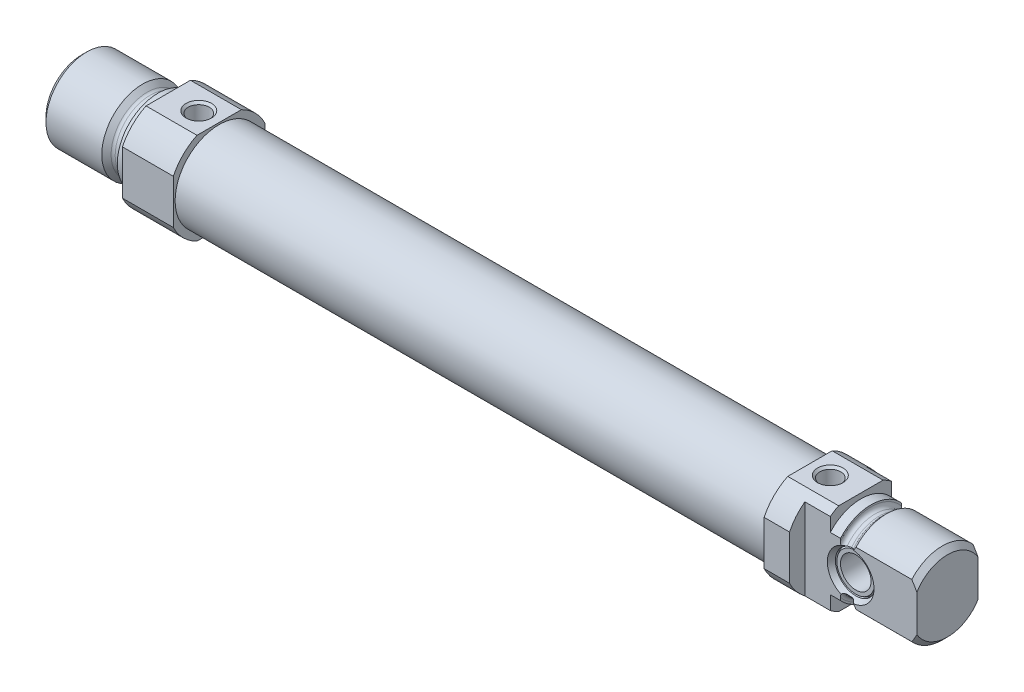
SolidWorks part; units mm, degrees
ref_plane "Front Plane" through (0, 0, 0) normal (0, 0, 1) x (1, 0, 0)
ref_plane "Top Plane" through (0, 0, 0) normal (0, 1, 0) x (1, 0, 0)
ref_plane "Right Plane" through (0, 0, 0) normal (1, 0, 0) x (0, 0, -1)
sketch "Sketch1" plane through (0, 0, 0) normal (0, 0, 1) x (1, 0, 0)
  line L0 (0, 0) -> (0, 7)
  line L1 (0, 7) -> (1, 8)
  line L2 (1, 8) -> (11.95, 8)
  line L3 (11.95, 8) -> (12.8657, 7.0843)
  line L4 (13.4314, 6.85) -> (14.2, 6.85)
  line L5 (15, 7.65) -> (15, 8)
  line L6 (15, 8) -> (17, 8)
  line L7 (17, 8) -> (17, 0)
  line L8 (17, 0) -> (0, 0)
  line L9 (17, 0) -> (0, 0) construction
  arc A0 (12.8657, 7.0843) -> (13.4314, 6.85) centre (13.4314, 7.65) ccw
  arc A1 (14.2, 6.85) -> (15, 7.65) centre (14.2, 7.65) ccw
revolve "Revolve1" add sketch "Sketch1" angle 360 about L9 reverse direction yes
cosmetic thread "Cosmetic Thread1" parameters "D1"=11.87, "D2"=14.16
ref_plane "Plane1" through (21.1, 0, 0) normal (1, 0, 0) x (0, 0, -1)
ref_plane "Plane2" through (9, 0, 0) normal (1, 0, 0) x (0, 0, -1)
ref_plane "Plane3" through (0, -11, 0) normal (0, 1, 0) x (1, 0, 0)
ref_plane "Plane4" through (0, 11, 0) normal (0, 1, 0) x (1, 0, 0)
ref_plane "Plane5" through (0, 0, 0) normal (0, 1, 0) x (1, 0, 0)
ref_plane "Plane6" through (0, 0, 0) normal (0, 1, 0) x (1, 0, 0)
ref_plane "Plane7" through (17, 0, 0) normal (1, 0, 0) x (0, 0, -1)
ref_plane "Plane8" through (17, 0, 0) normal (1, 0, 0) x (0, 0, -1)
ref_plane "Plane9" through (27, 0, 0) normal (1, 0, 0) x (0, 0, -1)
ref_plane "Plane10" through (17, 0, 0) normal (1, 0, 0) x (0, 0, -1)
ref_plane "Plane11" through (17, 0, 0) normal (1, 0, 0) x (0, 0, -1)
sketch "Sketch2" plane through (17, 0, 0) normal (1, 0, 0) x (0, 0, -1)
  line L0 (-4.3589, -9) -> (4.3589, -9)
  line L1 (9, -4.3589) -> (9, 4.3589)
  line L2 (4.3589, 9) -> (-4.3589, 9)
  line L3 (-9, 4.3589) -> (-9, -4.3589)
  arc A0 (-9, -4.3589) -> (-4.3589, -9) centre (0, 0) ccw
  arc A1 (4.3589, -9) -> (9, -4.3589) centre (0, 0) ccw
  arc A2 (9, 4.3589) -> (4.3589, 9) centre (0, 0) ccw
  arc A3 (-4.3589, 9) -> (-9, 4.3589) centre (0, 0) ccw
extrude "Boss-Extrude1" add sketch "Sketch2" along normal blind 10
ref_plane "Plane12" through (23, 0, 0) normal (1, 0, 0) x (0, 0, -1)
ref_plane "Plane13" through (0, 0, 0) normal (0, 0, 1) x (1, 0, 0)
ref_plane "Plane14" through (0, 0, -5.8) normal (0, 0, 1) x (1, 0, 0)
ref_plane "Plane15" through (0, 0, 0) normal (0, 1, 0) x (1, 0, 0)
ref_plane "Plane16" through (0, 4.5, 0) normal (0, 1, 0) x (1, 0, 0)
ref_plane "Plane17" through (0, 0, -6.6) normal (0, 0, 1) x (1, 0, 0)
ref_plane "Plane18" through (0, 0, 0) normal (0, 1, 0) x (1, 0, 0)
ref_plane "Plane19" through (0, 4.5, 0) normal (0, 1, 0) x (1, 0, 0)
ref_plane "Plane20" through (0, 5.493, -0.9686) normal (0, 0.9848, -0.1736) x (1, 0, 0)
ref_plane "Plane21" through (0, 4.0158, -0.7081) normal (0, 0.9848, -0.1736) x (1, 0, 0)
sketch "Sketch3" plane through (0, 0, 0) normal (0, 0, 1) x (1, 0, 0)
  line L0 (27, 0) -> (27, 8.65)
  line L1 (27, 8.65) -> (143, 8.65)
  line L2 (143, 8.65) -> (143, 0)
  line L3 (143, 0) -> (27, 0)
  line L4 (143, 0) -> (27, 0) construction
revolve "Revolve2" add sketch "Sketch3" angle 360 about L4 reverse direction yes
ref_plane "Plane22" through (143, 0, 0) normal (1, 0, 0) x (0, 0, -1)
sketch "Sketch4" plane through (143, 0, 0) normal (1, 0, 0) x (0, 0, -1)
  line L0 (-9, -9) -> (9, -9)
  line L1 (9, -9) -> (9, 9)
  line L2 (9, 9) -> (-9, 9)
  line L3 (-9, 9) -> (-9, -9)
extrude "Boss-Extrude2" add sketch "Sketch4" along normal blind 10
sketch "Sketch5" plane through (0, 0, 0) normal (0, 0, 1) x (1, 0, 0)
  line L0 (143, 20) -> (143, 10)
  line L1 (143, 10) -> (153, 10)
  line L2 (153, 10) -> (153, 20)
  line L3 (153, 20) -> (143, 20)
  line L4 (153, 0) -> (143, 0) construction
revolve "Cut-Revolve1" cut sketch "Sketch5" angle 360 about L4 reverse direction yes
ref_plane "Plane23" through (145.3, 0, 0) normal (1, 0, 0) x (0, 0, -1)
ref_plane "Plane24" through (147, 0, 0) normal (1, 0, 0) x (0, 0, -1)
ref_plane "Plane25" through (0, 0, 6.6) normal (0, 0, 1) x (1, 0, 0)
ref_plane "Plane26" through (0, 0, 0) normal (0, 1, 0) x (1, 0, 0)
ref_plane "Plane27" through (0, 4.5, 0) normal (0, 1, 0) x (1, 0, 0)
ref_plane "Plane28" through (0, 5.493, 0.9686) normal (0, 0.9848, 0.1736) x (1, 0, 0)
ref_plane "Plane29" through (0, 4.0158, 0.7081) normal (0, 0.9848, 0.1736) x (1, 0, 0)
ref_plane "Plane30" through (191, 0, 0) normal (1, 0, 0) x (0, 0, -1)
sketch "Sketch6" plane through (0, 0, 0) normal (0, 0, 1) x (1, 0, 0)
  line L0 (153, 0) -> (153, 8)
  line L1 (153, 8) -> (155, 8)
  line L2 (155, 8) -> (155, 7.65)
  line L3 (155.8, 6.85) -> (156.5686, 6.85)
  line L4 (157.1343, 7.0843) -> (158.05, 8)
  line L5 (158.05, 8) -> (169, 8)
  line L6 (169, 8) -> (170, 7)
  line L7 (170, 7) -> (170, 0)
  line L8 (170, 0) -> (153, 0)
  line L9 (170, 0) -> (153, 0) construction
  arc A0 (155, 7.65) -> (155.8, 6.85) centre (155.8, 7.65) ccw
  arc A1 (156.5686, 6.85) -> (157.1343, 7.0843) centre (156.5686, 7.65) ccw
revolve "Revolve3" add sketch "Sketch6" angle 360 about L9 reverse direction yes
cosmetic thread "Cosmetic Thread2" parameters "D1"=11.87, "D2"=14.16
ref_plane "Plane31" through (181, 0, 0) normal (1, 0, 0) x (0, 0, -1)
ref_plane "Plane32" through (191, 0, 0) normal (1, 0, 0) x (0, 0, -1)
ref_plane "Plane33" through (191, 0, 0) normal (1, 0, 0) x (0, 0, -1)
sketch "Sketch7" plane through (0, 0, 0) normal (0, 1, 0) x (1, 0, 0)
  line L0 (148, 18) -> (148, 6)
  line L1 (148, 6) -> (170, 6)
  line L2 (170, 6) -> (170, -6)
  line L3 (170, -6) -> (148, -6)
  line L4 (148, -6) -> (148, -18)
  line L5 (148, -18) -> (182, -18)
  line L6 (182, -18) -> (182, 18)
  line L7 (182, 18) -> (148, 18)
extrude "Cut-Extrude1" cut sketch "Sketch7" along normal blind 10 and the other way blind 10
ref_plane "Plane34" through (157, 0, 0) normal (1, 0, 0) x (0, 0, -1)
sketch "Sketch8" plane through (157, 0, 0) normal (1, 0, 0) x (0, 0, -1)
  line L0 (-6.2, 0) -> (-6.2, 4.6928)
  line L1 (-6.2, 4.6928) -> (-5, 4)
  line L2 (-5, 4) -> (-4.5, 4)
  line L3 (-4.5, 4) -> (-5, 3.7113)
  line L4 (-5, 3.7113) -> (-5, 3)
  line L5 (-5, 3) -> (5, 3)
  line L6 (5, 3) -> (5, 3.7113)
  line L7 (5, 3.7113) -> (4.5, 4)
  line L8 (4.5, 4) -> (5, 4)
  line L9 (5, 4) -> (6.2, 4.6928)
  line L10 (6.2, 4.6928) -> (6.2, 0)
  line L11 (6.2, 0) -> (-6.2, 0)
  line L12 (5, 0) -> (-6.2, 0) construction
revolve "Cut-Revolve2" cut sketch "Sketch8" angle 360 about L12 reverse direction yes
hole_wizard "Hole1" positions "Sketch10" profile "Sketch9" legacy
sketch "Sketch10" plane through (0, 9, 0) normal (0, 1, 0) x (1, 0, 0)
  point P0 (23, 0)
sketch "Sketch9" plane through (23, 9, 0) normal (1, 0, 0) x (0, 0, 1)
  line L0 (0, 0) -> (0, 9)
  line L1 (0, 9) -> (2.067, 9)
  line L2 (2.067, 9) -> (2.067, 0.433)
  line L3 (2.067, 0.433) -> (2.5, 0)
  line L4 (2.5, 0) -> (0, 0)
  line L5 (0, -6.4453) -> (0, 115.525) construction
  line L6 (-2.067, 0.433) -> (-2.5, 0) construction
  dimension "Diameter" = 4.134
  dimension "Depth" = 9
  dimension "C-Sink Angle" = 90
  dimension "C-Sink Diameter" = 5
cosmetic thread "Cosmetic Thread3" parameters "D1"=7, "D2"=5
hole_wizard "Hole2" positions "Sketch12" profile "Sketch11" legacy
sketch "Sketch12" plane through (0, 9, 0) normal (0, 1, 0) x (1, 0, 0)
  point P0 (147, 0)
sketch "Sketch11" plane through (147, 9, 0) normal (1, 0, 0) x (0, 0, 1)
  line L0 (0, 0) -> (0, 12.1934)
  line L1 (0, 12.1934) -> (2.067, 11)
  line L2 (2.067, 11) -> (2.067, 0.433)
  line L3 (2.067, 0.433) -> (2.5, 0)
  line L4 (2.5, 0) -> (0, 0)
  line L5 (0, -14.3089) -> (0, 102.4216) construction
  line L6 (0, 12.1934) -> (-2.067, 11) construction
  line L7 (-2.067, 0.433) -> (-2.5, 0) construction
  dimension "Diameter" = 4.134
  dimension "Depth" = 11
  dimension "C-Sink Diameter" = 5
  dimension "C-Sink Angle" = 90
  dimension "Drill Angle" = 120
cosmetic thread "Cosmetic Thread4" parameters "D1"=6, "D2"=5
sketch "Sketch13" plane through (0, 0, 0) normal (0, 0, 1) x (1, 0, 0)
  line L0 (-5, 0) -> (-5, 3)
  line L1 (-5, 3) -> (41.2, 3)
  line L2 (41.2, 3) -> (41.2, 8)
  line L3 (41.2, 8) -> (125.2, 8)
  line L4 (125.2, 8) -> (125.2, 0)
  line L5 (125.2, 0) -> (-5, 0)
  line L6 (125.2, 0) -> (-5, 0) construction
revolve "Cut-Revolve3" cut sketch "Sketch13" angle 360 about L6 reverse direction yes
ref_plane "Plane35" through (-5, 0, 0) normal (1, 0, 0) x (0, 0, -1)
ref_plane "Plane36" through (0, 9, 0) normal (0, 1, 0) x (1, 0, 0)
ref_plane "Plane37" through (8, 0, 0) normal (1, 0, 0) x (0, 0, -1)
ref_plane "Plane38" through (0, 0, 0) normal (1, 0, 0) x (0, 0, -1)
ref_plane "Plane39" through (17, 0, 0) normal (1, 0, 0) x (0, 0, -1)
ref_plane "Plane40" through (153, 0, 0) normal (1, 0, 0) x (0, 0, -1)
ref_plane "Plane41" through (17, 0, 0) normal (1, 0, 0) x (0, 0, -1)
ref_plane "Plane42" through (0, 9, 0) normal (0, 1, 0) x (1, 0, 0)
ref_plane "Plane43" through (36.5, 0, 0) normal (1, 0, 0) x (0, 0, -1)
ref_plane "Plane44" through (133.5, 0, 0) normal (1, 0, 0) x (0, 0, -1)
ref_plane "Plane45" through (0, 0, 0) normal (0, 0, 1) x (1, 0, 0)
ref_plane "Plane46" through (17, 0, 0) normal (1, 0, 0) x (0, 0, -1)
ref_plane "Plane47" through (0, 9, 0) normal (0, 1, 0) x (1, 0, 0)
ref_plane "Plane48" through (3, 0, 0) normal (1, 0, 0) x (0, 0, -1)
ref_plane "Plane49" through (0, 9, 0) normal (0, 1, 0) x (1, 0, 0)
ref_plane "FDT_FRONT XY" through (17, 0, 0) normal (1, 0, 0) x (0, 0, -1)
ref_plane "FDT_FRONT XZ" through (0, 0, 0) normal (0, -1, 0) x (-1, 0, 0)
ref_plane "FDT_FRONT YZ" through (0, 0, 0) normal (0, 0, -1) x (-1, 0, 0)
ref_axis "FDT_FRONT X" through (17, 0, 80.9) along (0, 0, -1)
ref_axis "FDT_FRONT Y" through (17, -50, 0) along (0, 1, 0)
ref_axis "FDT_FRONT Z" through (80.9, 0, 0) along (-1, 0, 0)
sketch3d "FDT_FRONT"
  point P0 (17, 0, 0)
ref_plane "FDT_QSFRONT XY" through (0, 9, 0) normal (0, 1, 0) x (1, 0, 0)
ref_plane "FDT_QSFRONT XZ" through (23, 0, 0) normal (-1, 0, 0) x (0, 0, 1)
ref_plane "FDT_QSFRONT YZ" through (0, 0, 0) normal (0, 0, 1) x (1, 0, 0)
ref_axis "FDT_QSFRONT X" through (23, 9, -50) along (0, 0, 1)
ref_axis "FDT_QSFRONT Y" through (-80.9, 9, 0) along (1, 0, 0)
ref_axis "FDT_QSFRONT Z" through (23, 50, 0) along (0, -1, 0)
sketch3d "FDT_QSFRONT"
  point P0 (23, 9, 0)
ref_plane "FDT_QSREAR XY" through (0, 9, 0) normal (0, 1, 0) x (1, 0, 0)
ref_plane "FDT_QSREAR XZ" through (147, 0, 0) normal (-1, 0, 0) x (0, 0, 1)
ref_plane "FDT_QSREAR YZ" through (0, 0, 0) normal (0, 0, 1) x (1, 0, 0)
ref_axis "FDT_QSREAR X" through (147, 9, -50) along (0, 0, 1)
ref_axis "FDT_QSREAR Y" through (-80.9, 9, 0) along (1, 0, 0)
ref_axis "FDT_QSREAR Z" through (147, 50, 0) along (0, -1, 0)
sketch3d "FDT_QSREAR"
  point P0 (147, 9, 0)
ref_plane "FDT_REAR XY" through (153, 0, 0) normal (-1, 0, 0) x (0, 0, 1)
ref_plane "FDT_REAR XZ" through (0, 0, 0) normal (0, 1, 0) x (1, 0, 0)
ref_plane "FDT_REAR YZ" through (0, 0, 0) normal (0, 0, -1) x (-1, 0, 0)
ref_axis "FDT_REAR X" through (153, 0, 80.9) along (0, 0, -1)
ref_axis "FDT_REAR Y" through (153, 50, 0) along (0, -1, 0)
ref_axis "FDT_REAR Z" through (-80.9, 0, 0) along (1, 0, 0)
sketch3d "FDT_REAR"
  point P0 (153, 0, 0)
ref_plane "FDT_SMBR1 XY" through (36.5, 0, 0) normal (-1, 0, 0) x (0, 0, 1)
ref_plane "FDT_SMBR1 XZ" through (0, 0, 0) normal (0, -1, 0) x (-1, 0, 0)
ref_plane "FDT_SMBR1 YZ" through (0, 0, 0) normal (0, 0, 1) x (1, 0, 0)
ref_axis "FDT_SMBR1 X" through (36.5, 0, -80.9) along (0, 0, 1)
ref_axis "FDT_SMBR1 Y" through (36.5, -50, 0) along (0, 1, 0)
ref_axis "FDT_SMBR1 Z" through (-80.9, 0, 0) along (1, 0, 0)
sketch3d "FDT_SMBR1"
  point P0 (36.5, 0, 0)
ref_plane "FDT_SMBR2 XY" through (133.5, 0, 0) normal (-1, 0, 0) x (0, 0, 1)
ref_plane "FDT_SMBR2 XZ" through (0, 0, 0) normal (0, -1, 0) x (-1, 0, 0)
ref_plane "FDT_SMBR2 YZ" through (0, 0, 0) normal (0, 0, 1) x (1, 0, 0)
ref_axis "FDT_SMBR2 X" through (133.5, 0, -80.9) along (0, 0, 1)
ref_axis "FDT_SMBR2 Y" through (133.5, -50, 0) along (0, 1, 0)
ref_axis "FDT_SMBR2 Z" through (-80.9, 0, 0) along (1, 0, 0)
sketch3d "FDT_SMBR2"
  point P0 (133.5, 0, 0)
ref_plane "FDT_SWIVELAXIS XY" through (0, 0, 0) normal (0, 0, 1) x (1, 0, 0)
ref_plane "FDT_SWIVELAXIS XZ" through (0, 0, 0) normal (0, -1, 0) x (-1, 0, 0)
ref_plane "FDT_SWIVELAXIS YZ" through (157, 0, 0) normal (1, 0, 0) x (0, 0, -1)
ref_axis "FDT_SWIVELAXIS X" through (-80.9, 0, 0) along (1, 0, 0)
ref_axis "FDT_SWIVELAXIS Y" through (157, -50, 0) along (0, 1, 0)
ref_axis "FDT_SWIVELAXIS Z" through (157, 0, 80.9) along (0, 0, -1)
sketch3d "FDT_SWIVELAXIS"
  point P0 (157, 0, 0)
ref_plane "NUT XY" through (8, 0, 0) normal (1, 0, 0) x (0, 0, -1)
ref_plane "NUT XZ" through (0, 0, 0) normal (0, -1, 0) x (-1, 0, 0)
ref_plane "NUT YZ" through (0, 0, 0) normal (0, 0, -1) x (-1, 0, 0)
ref_axis "NUT X" through (8, 0, 80.9) along (0, 0, -1)
ref_axis "NUT Y" through (8, -50, 0) along (0, 1, 0)
ref_axis "NUT Z" through (80.9, 0, 0) along (-1, 0, 0)
sketch3d "NUT"
  point P0 (8, 0, 0)
ref_plane "ZR XY" through (0, 0, 0) normal (-1, 0, 0) x (0, 0, 1)
ref_plane "ZR XZ" through (0, 0, 0) normal (0, 1, 0) x (1, 0, 0)
ref_plane "ZR YZ" through (0, 0, 0) normal (0, 0, -1) x (-1, 0, 0)
ref_axis "ZR X" through (0, 0, 80.9) along (0, 0, -1)
ref_axis "ZR Y" through (0, 50, 0) along (0, -1, 0)
ref_axis "ZR Z" through (-80.9, 0, 0) along (1, 0, 0)
sketch3d "ZR"
  point P0 (0, 0, 0)
ref_plane "ZYL XY" through (17, 0, 0) normal (1, 0, 0) x (0, 0, -1)
ref_plane "ZYL XZ" through (0, 0, 0) normal (0, -1, 0) x (-1, 0, 0)
ref_plane "ZYL YZ" through (0, 0, 0) normal (0, 0, -1) x (-1, 0, 0)
ref_axis "ZYL X" through (17, 0, 80.9) along (0, 0, -1)
ref_axis "ZYL Y" through (17, -50, 0) along (0, 1, 0)
ref_axis "ZYL Z" through (80.9, 0, 0) along (-1, 0, 0)
sketch3d "ZYL"
  point P0 (17, 0, 0)
